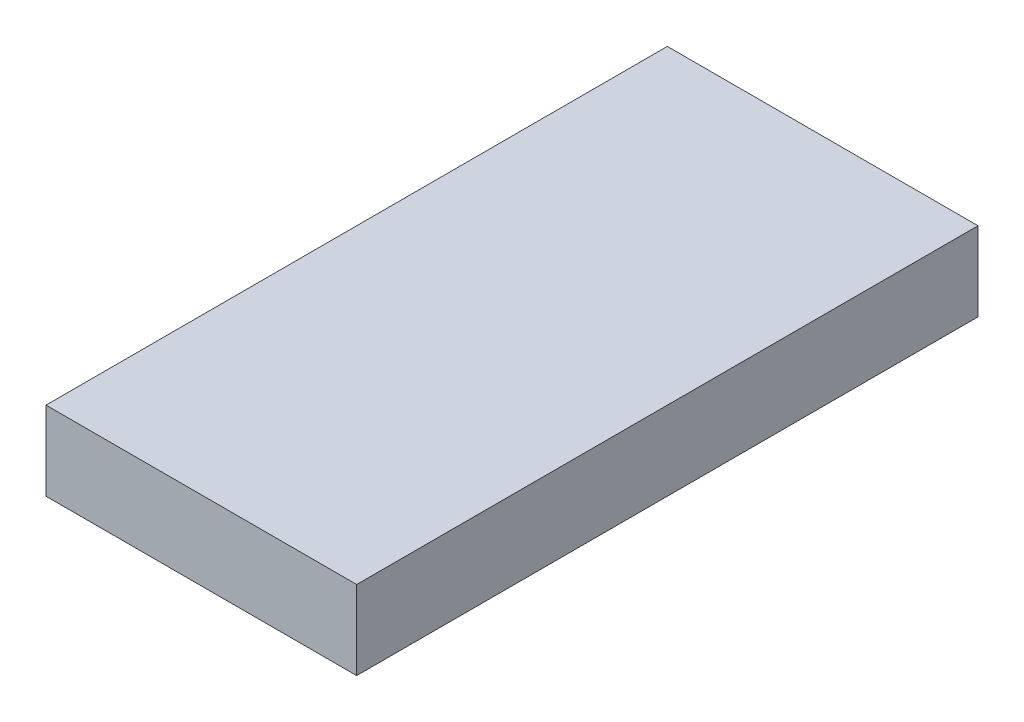
SolidWorks part; units mm, degrees
ref_plane "Front Plane" through (0, 0, 0) normal (0, 0, 1) x (1, 0, 0)
ref_plane "Top Plane" through (0, 0, 0) normal (0, 1, 0) x (1, 0, 0)
ref_plane "Right Plane" through (0, 0, 0) normal (1, 0, 0) x (0, 0, -1)
sketch "Sketch1" plane through (0, 0, 0) normal (0, 1, 0) x (1, 0, 0)
  line L1 (25, -50) -> (-25, -50)
  line L2 (25, -50) -> (25, 50)
  line L3 (25, 50) -> (-25, 50)
  line L4 (-25, -50) -> (-25, 50)
  line L5 (25, -50) -> (-25, 50) construction
  line L6 (25, 50) -> (-25, -50) construction
  point P0 (0, 0)
  dimension "D1" = 50
  dimension "D2" = 100
extrude "Boss-Extrude1" add sketch "Sketch1" along normal blind 12.7
